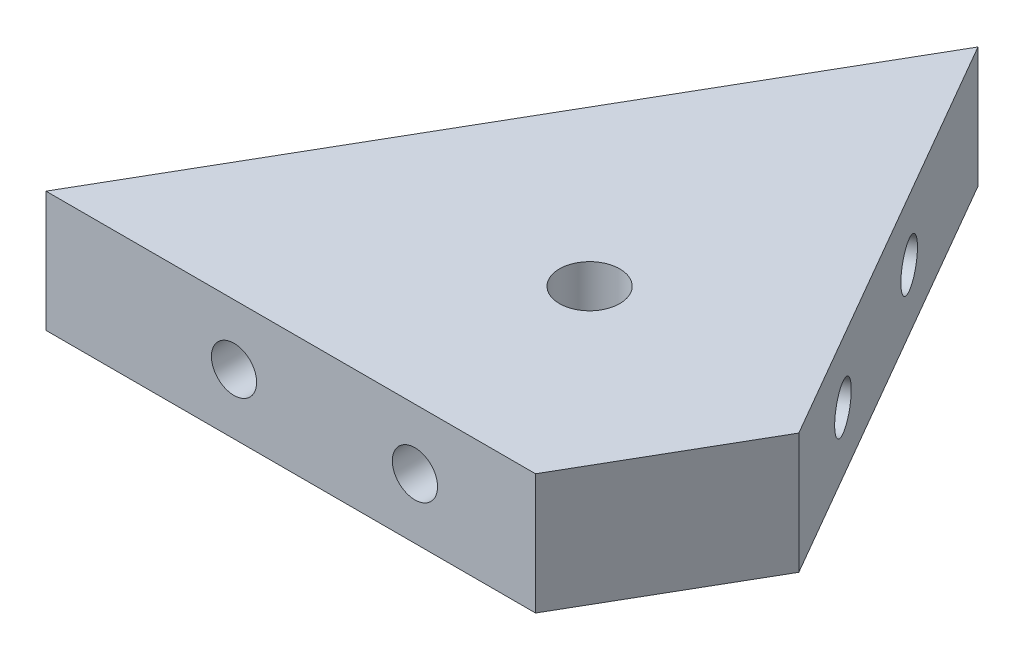
SolidWorks part; units mm, degrees
material "1023 Carbon Steel Sheet (SS)"
ref_plane "Front Plane" through (0, 0, 0) normal (0, 0, 1) x (1, 0, 0)
ref_plane "Top Plane" through (0, 0, 0) normal (0, 1, 0) x (1, 0, 0)
ref_plane "Right Plane" through (0, 0, 0) normal (1, 0, 0) x (0, 0, -1)
sketch "Sketch1" plane through (0, 0, 0) normal (0, 1, 0) x (1, 0, 0)
  line L0 (159.6594, -241.1624) -> (-297.5406, 22.8022) construction
  line L1 (-145.1406, 286.7667) -> (-449.9406, -241.1624) construction
  line L2 (-449.9406, -241.1624) -> (159.6594, -241.1624) construction
  line L3 (159.6594, -241.1624) -> (-145.1406, 286.7667) construction
  line L4 (93.6683, -241.1624) -> (93.6683, -203.0624) construction
  line L5 (119.0683, -241.1624) -> (129.2161, -223.5859)
  line L6 (55.5683, -241.1624) -> (55.5683, -181.0653) construction
  line L7 (15.9736, -241.1624) -> (51.8951, -178.9446)
  line L8 (15.9736, -241.1624) -> (119.0683, -241.1624)
  line L9 (51.8951, -178.9446) -> (129.2161, -223.5859)
  line L10 (93.6683, -203.0624) -> (55.5683, -203.0624) construction
  dimension "D1" = 609.6
  dimension "D2" = 38.1
  dimension "D3" = 25.4
  dimension "D4" = 38.1
  dimension "D6" = 40.5911
  dimension "D5" = 15.24
  dimension "D7" = 103.0947
extrude "Boss-Extrude1" add sketch "Sketch1" along normal blind 25.4
sketch "Sketch2" plane through (0, 0, 241.1624) normal (0, 0, 1) x (1, 0, 0)
  line L0 (15.9736, 0) -> (119.0683, 0) construction
  line L1 (15.9736, 0) -> (15.9736, 25.4) construction
  line L2 (119.0683, 0) -> (119.0683, 25.4) construction
  line L3 (15.9736, 25.4) -> (119.0683, 25.4) construction
  line L4 (15.9736, 0) -> (119.0683, 25.4) construction
  line L5 (119.0683, 0) -> (15.9736, 25.4) construction
  line L6 (93.6683, 25.4) -> (93.6683, 0) construction
  line L7 (55.5683, 0) -> (55.5683, 25.4) construction
  circle A0 centre (55.5683, 12.7) radius 4.7625
  circle A1 centre (93.6683, 12.7) radius 4.7625
  point P6 (67.521, 12.7)
  dimension "D4" = 9.525
  dimension "D5" = 9.525
  dimension "D1" = 25.4
  dimension "D2" = 25.4
  dimension "D3" = 38.1
extrude "Cut-Extrude1" cut sketch "Sketch2" against normal blind 12.7
sketch "Sketch3" plane through (0, 0, 228.4624) normal (0, 0, 1) x (1, 0, 0)
  circle A0 centre (55.5683, 12.7) radius 3.9687
  dimension "D1" = 7.9375
extrude "Cut-Extrude2" cut sketch "Sketch3" against normal blind 12.7
sketch "Sketch4" plane through (0, 0, 228.4624) normal (0, 0, 1) x (1, 0, 0)
  circle A0 centre (93.6683, 12.7) radius 3.9688
  dimension "D1" = 7.9375
extrude "Cut-Extrude3" cut sketch "Sketch4" against normal blind 12.7
mirror "Mirror1" about plane through (51.8951, 25.4, 178.9446) normal (-0.5, 0, 0.866) of "Boss-Extrude1", "Cut-Extrude1", "Cut-Extrude2", "Cut-Extrude3"
sketch "Sketch5" plane through (0, 25.4, 0) normal (0, 1, 0) x (1, 0, 0)
  line L0 (87.8165, -116.7268) -> (15.9736, -241.1624) construction
  line L1 (15.9736, -241.1624) -> (119.0683, -241.1624) construction
  line L2 (119.0683, -241.1624) -> (139.3639, -206.0094) construction
  line L3 (139.3639, -206.0094) -> (87.8165, -116.7268) construction
  line L4 (51.8951, -178.9446) -> (129.2161, -223.5859) construction
  circle A0 centre (90.5556, -201.2653) radius 6.35
  dimension "D1" = 12.7
extrude "Cut-Extrude4" cut sketch "Sketch5" against normal through all
equation "\"bplate_length\"= 24in"
equation "\"bplate_height\"= 6in"
equation "\"bplate_thickness\"= 0.5in"
equation "\"connector_plate_hole_diameter\"= 0.375in"
equation "\"connector_plate_hole_depth\"= 1in"
equation "\"connector_plate_thickness\"= 1in"
equation "\"D1@Sketch1\"=\"bplate_length\""
